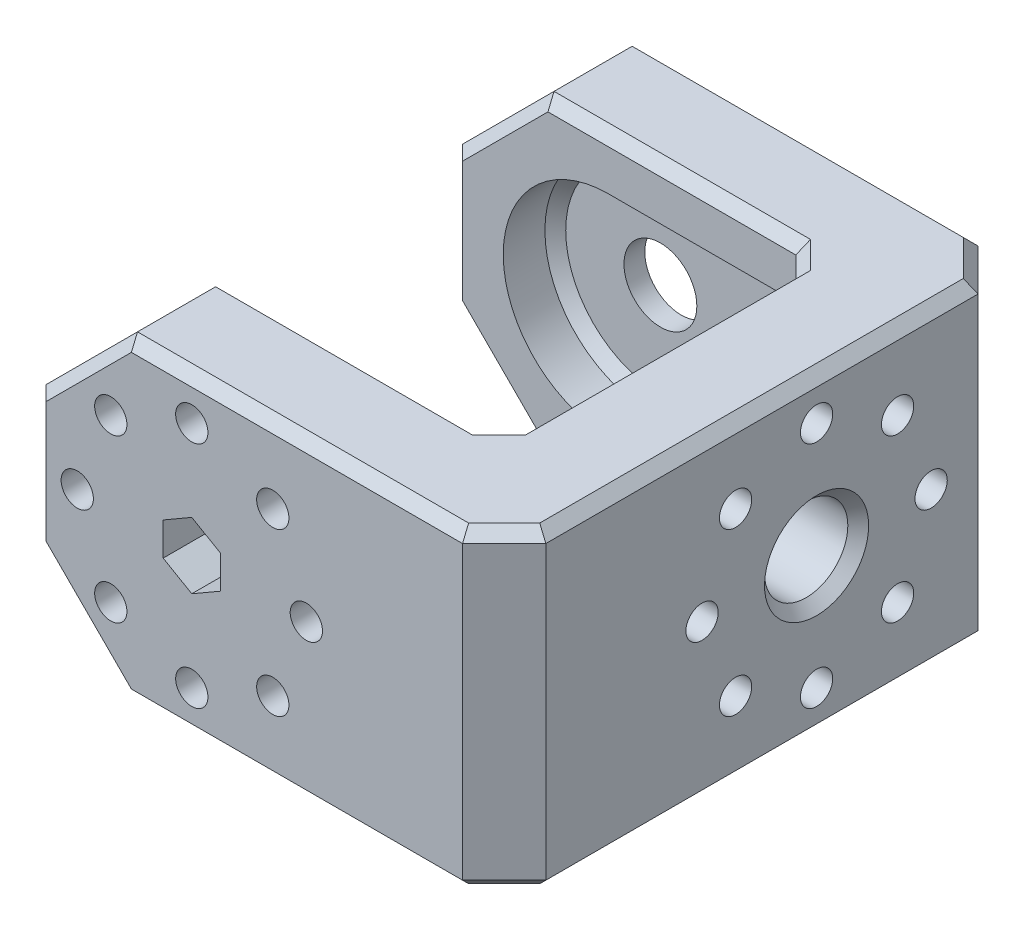
SolidWorks part; units mm, degrees
ref_plane "Alzado" through (0, 0, 0) normal (0, 0, 1) x (1, 0, 0)
ref_plane "Planta" through (0, 0, 0) normal (0, 1, 0) x (1, 0, 0)
ref_plane "Vista lateral" through (0, 0, 0) normal (1, 0, 0) x (0, 0, -1)
sketch "Croquis1" plane through (0, 0, 0) normal (0, 0, 1) x (1, 0, 0)
  line L0 (6.2132, 15) -> (30, 15)
  line L1 (15, -6.2132) -> (15, 6.2132) construction
  line L2 (15, 6.2132) -> (6.2132, 15) construction
  line L3 (6.2132, 15) -> (-6.2132, 15)
  line L4 (-6.2132, 15) -> (-15, 6.2132)
  line L5 (-15, 6.2132) -> (-15, -6.2132)
  line L6 (-15, -6.2132) -> (-6.2132, -15)
  line L7 (-6.2132, -15) -> (6.2132, -15)
  line L8 (6.2132, -15) -> (15, -6.2132) construction
  line L9 (30, 15) -> (30, -15)
  line L10 (30, -15) -> (6.2132, -15)
  circle A0 centre (0, 0) radius 15 construction
  dimension "D1" = 30
  dimension "D2" = 15
extrude "Saliente-Extruir1" add sketch "Croquis1" along normal blind 60
sketch "Croquis2" plane through (0, 15, 0) normal (0, 1, 0) x (1, 0, 0)
  line L0 (-15, -60) -> (-15, 0) construction
  line L1 (-15, -50.5) -> (20, -50.5)
  line L2 (-15, -50.5) -> (-15, -20)
  line L3 (-15, -20) -> (20, -20)
  line L4 (20, -50.5) -> (20, -20)
  line L5 (30, 0) -> (-6.2132, 0) construction
  line L6 (-15, -10.5) -> (20, -10.5)
  line L7 (-15, -10.5) -> (-15, 0)
  line L8 (-15, 0) -> (20, 0)
  line L9 (20, -10.5) -> (20, 0)
  line L10 (30, -60) -> (-6.2132, -60) construction
  line L11 (30, -60) -> (30, 0) construction
  dimension "D1" = 9.5
  dimension "D2" = 30.5
  dimension "D3" = 9.5
  dimension "D4" = 10
extrude "Cortar-Extruir1" cut sketch "Croquis2" against normal through all
sketch "Croquis3" plane through (0, 0, 60) normal (0, 0, 1) x (1, 0, 0)
  circle A0 centre (0, 0) radius 1.5
  dimension "D1" = 3
extrude "Cortar-Extruir2" cut sketch "Croquis3" against normal up to next
sketch "Croquis4" plane through (0, 0, 20) normal (0, 0, 1) x (1, 0, 0)
  line L0 (0, 10.0902) -> (20, 10.0902)
  line L1 (20, -15) -> (20, 15) construction
  line L2 (20, 10.0902) -> (20, -10.0902)
  line L3 (20, -10.0902) -> (0, -10.0902)
  arc A0 (0, 10.0902) -> (0, -10.0902) centre (0, 0) ccw
extrude "Cortar-Extruir3" cut sketch "Croquis4" against normal blind 5
sketch "Croquis5" plane through (30, 0, 0) normal (1, 0, 0) x (0, 0, -1)
  line L0 (-60, 0) -> (49940, 0) construction
  line L1 (-60, -15) -> (-60, 15) construction
  line L2 (-30, 15) -> (-30, -49985) construction
  line L3 (-60, 15) -> (0, 15) construction
  circle A0 centre (-30, 0) radius 4
  circle A1 centre (-30, 0) radius 11 construction
  circle A2 centre (-30, 11) radius 1.55
  circle A3 centre (-22.2218, 7.7782) radius 1.55
  circle A4 centre (-19, 0) radius 1.55
  circle A5 centre (-22.2218, -7.7782) radius 1.55
  circle A6 centre (-30, -11) radius 1.55
  circle A7 centre (-37.7782, -7.7782) radius 1.55
  circle A8 centre (-41, 0) radius 1.55
  circle A9 centre (-37.7782, 7.7782) radius 1.55
  point P4 (-60, 0)
  point P9 (-30, 15)
  point P32 (-30, 0)
  dimension "D1" = 8
  dimension "D2" = 22
  dimension "D3" = 3.1
  dimension "D4" = 8
extrude "Cortar-Extruir4" cut sketch "Croquis5" against normal blind 10
sketch "Croquis6" plane through (20, 0, 0) normal (-1, 0, 0) x (0, 0, 1)
  line L0 (40.0235, 5.5328) -> (40.8454, 8.6)
  line L1 (33.1754, 11) -> (31.5877, 13.75)
  line L2 (31.5877, 13.75) -> (28.4123, 13.75)
  line L3 (28.4123, 13.75) -> (26.8246, 11)
  line L4 (26.8246, 11) -> (28.4123, 8.25)
  line L5 (28.4123, 8.25) -> (31.5877, 8.25)
  line L6 (31.5877, 8.25) -> (33.1754, 11)
  line L7 (40.8454, 8.6) -> (38.6, 10.8454)
  line L8 (38.6, 10.8454) -> (35.5328, 10.0235)
  line L9 (35.5328, 10.0235) -> (34.7109, 6.9563)
  line L10 (34.7109, 6.9563) -> (36.9563, 4.7109)
  line L11 (36.9563, 4.7109) -> (40.0235, 5.5328)
  line L12 (41, -3.1754) -> (43.75, -1.5877)
  line L13 (43.75, -1.5877) -> (43.75, 1.5877)
  line L14 (43.75, 1.5877) -> (41, 3.1754)
  line L15 (41, 3.1754) -> (38.25, 1.5877)
  line L16 (38.25, 1.5877) -> (38.25, -1.5877)
  line L17 (38.25, -1.5877) -> (41, -3.1754)
  line L18 (35.5328, -10.0235) -> (38.6, -10.8454)
  line L19 (38.6, -10.8454) -> (40.8454, -8.6)
  line L20 (40.8454, -8.6) -> (40.0235, -5.5328)
  line L21 (40.0235, -5.5328) -> (36.9563, -4.7109)
  line L22 (36.9563, -4.7109) -> (34.7109, -6.9563)
  line L23 (34.7109, -6.9563) -> (35.5328, -10.0235)
  line L24 (26.8246, -11) -> (28.4123, -13.75)
  line L25 (28.4123, -13.75) -> (31.5877, -13.75)
  line L26 (31.5877, -13.75) -> (33.1754, -11)
  line L27 (33.1754, -11) -> (31.5877, -8.25)
  line L28 (31.5877, -8.25) -> (28.4123, -8.25)
  line L29 (28.4123, -8.25) -> (26.8246, -11)
  line L30 (19.9765, -5.5328) -> (19.1546, -8.6)
  line L31 (19.1546, -8.6) -> (21.4, -10.8454)
  line L32 (21.4, -10.8454) -> (24.4672, -10.0235)
  line L33 (24.4672, -10.0235) -> (25.2891, -6.9563)
  line L34 (25.2891, -6.9563) -> (23.0437, -4.7109)
  line L35 (23.0437, -4.7109) -> (19.9765, -5.5328)
  line L36 (19, 3.1754) -> (16.25, 1.5877)
  line L37 (16.25, 1.5877) -> (16.25, -1.5877)
  line L38 (16.25, -1.5877) -> (19, -3.1754)
  line L39 (19, -3.1754) -> (21.75, -1.5877)
  line L40 (21.75, -1.5877) -> (21.75, 1.5877)
  line L41 (21.75, 1.5877) -> (19, 3.1754)
  line L42 (24.4672, 10.0235) -> (21.4, 10.8454)
  line L43 (21.4, 10.8454) -> (19.1546, 8.6)
  line L44 (19.1546, 8.6) -> (19.9765, 5.5328)
  line L45 (19.9765, 5.5328) -> (23.0437, 4.7109)
  line L46 (23.0437, 4.7109) -> (25.2891, 6.9563)
  line L47 (25.2891, 6.9563) -> (24.4672, 10.0235)
  circle A0 centre (30, 11) radius 2.75 construction
  circle A1 centre (37.7782, 7.7782) radius 2.75 construction
  circle A2 centre (41, 0) radius 2.75 construction
  circle A3 centre (37.7782, -7.7782) radius 2.75 construction
  circle A4 centre (30, -11) radius 2.75 construction
  circle A5 centre (22.2218, -7.7782) radius 2.75 construction
  circle A6 centre (19, 0) radius 2.75 construction
  circle A7 centre (22.2218, 7.7782) radius 2.75 construction
  point P68 (30, 0)
  dimension "D1" = 5.5
  dimension "D2" = 8
extrude "Cortar-Extruir5" cut sketch "Croquis6" against normal blind 5
sketch "Croquis7" plane through (0, 0, 60) normal (0, 0, 1) x (1, 0, 0)
  circle A0 centre (0, 11) radius 1.55
  circle A1 centre (0, 0) radius 1.5 construction
  circle A2 centre (7.7782, 7.7782) radius 1.55
  circle A3 centre (11, 0) radius 1.55
  circle A4 centre (7.7782, -7.7782) radius 1.55
  circle A5 centre (0, -11) radius 1.55
  circle A6 centre (-7.7782, -7.7782) radius 1.55
  circle A7 centre (-11, 0) radius 1.55
  circle A8 centre (-7.7782, 7.7782) radius 1.55
  point P21 (0, 0)
  dimension "D1" = 11
  dimension "D3" = 3.1
  dimension "D2" = 8
extrude "Cortar-Extruir6" cut sketch "Croquis7" against normal up to next
sketch "Croquis8" plane through (0, 0, 50.5) normal (0, 0, -1) x (-1, 0, 0)
  line L0 (6.9563, 4.7109) -> (10.0235, 5.5328)
  line L1 (3.1754, 11) -> (1.5877, 13.75)
  line L2 (1.5877, 13.75) -> (-1.5877, 13.75)
  line L3 (-1.5877, 13.75) -> (-3.1754, 11)
  line L4 (-3.1754, 11) -> (-1.5877, 8.25)
  line L5 (-1.5877, 8.25) -> (1.5877, 8.25)
  line L6 (1.5877, 8.25) -> (3.1754, 11)
  line L7 (10.0235, 5.5328) -> (10.8454, 8.6)
  line L8 (10.8454, 8.6) -> (8.6, 10.8454)
  line L9 (8.6, 10.8454) -> (5.5328, 10.0235)
  line L10 (5.5328, 10.0235) -> (4.7109, 6.9563)
  line L11 (4.7109, 6.9563) -> (6.9563, 4.7109)
  line L12 (8.25, -1.5877) -> (11, -3.1754)
  line L13 (11, -3.1754) -> (13.75, -1.5877)
  line L14 (13.75, -1.5877) -> (13.75, 1.5877)
  line L15 (13.75, 1.5877) -> (11, 3.1754)
  line L16 (11, 3.1754) -> (8.25, 1.5877)
  line L17 (8.25, 1.5877) -> (8.25, -1.5877)
  line L18 (4.7109, -6.9563) -> (5.5328, -10.0235)
  line L19 (5.5328, -10.0235) -> (8.6, -10.8454)
  line L20 (8.6, -10.8454) -> (10.8454, -8.6)
  line L21 (10.8454, -8.6) -> (10.0235, -5.5328)
  line L22 (10.0235, -5.5328) -> (6.9563, -4.7109)
  line L23 (6.9563, -4.7109) -> (4.7109, -6.9563)
  line L24 (-1.5877, -8.25) -> (-3.1754, -11)
  line L25 (-3.1754, -11) -> (-1.5877, -13.75)
  line L26 (-1.5877, -13.75) -> (1.5877, -13.75)
  line L27 (1.5877, -13.75) -> (3.1754, -11)
  line L28 (3.1754, -11) -> (1.5877, -8.25)
  line L29 (1.5877, -8.25) -> (-1.5877, -8.25)
  line L30 (-6.9563, -4.7109) -> (-10.0235, -5.5328)
  line L31 (-10.0235, -5.5328) -> (-10.8454, -8.6)
  line L32 (-10.8454, -8.6) -> (-8.6, -10.8454)
  line L33 (-8.6, -10.8454) -> (-5.5328, -10.0235)
  line L34 (-5.5328, -10.0235) -> (-4.7109, -6.9563)
  line L35 (-4.7109, -6.9563) -> (-6.9563, -4.7109)
  line L36 (-8.25, 1.5877) -> (-11, 3.1754)
  line L37 (-11, 3.1754) -> (-13.75, 1.5877)
  line L38 (-13.75, 1.5877) -> (-13.75, -1.5877)
  line L39 (-13.75, -1.5877) -> (-11, -3.1754)
  line L40 (-11, -3.1754) -> (-8.25, -1.5877)
  line L41 (-8.25, -1.5877) -> (-8.25, 1.5877)
  line L42 (-4.7109, 6.9563) -> (-5.5328, 10.0235)
  line L43 (-5.5328, 10.0235) -> (-8.6, 10.8454)
  line L44 (-8.6, 10.8454) -> (-10.8454, 8.6)
  line L45 (-10.8454, 8.6) -> (-10.0235, 5.5328)
  line L46 (-10.0235, 5.5328) -> (-6.9563, 4.7109)
  line L47 (-6.9563, 4.7109) -> (-4.7109, 6.9563)
  circle A0 centre (0, 11) radius 2.75 construction
  circle A1 centre (7.7782, 7.7782) radius 2.75 construction
  circle A2 centre (11, 0) radius 2.75 construction
  circle A3 centre (7.7782, -7.7782) radius 2.75 construction
  circle A4 centre (0, -11) radius 2.75 construction
  circle A5 centre (-7.7782, -7.7782) radius 2.75 construction
  circle A6 centre (-11, 0) radius 2.75 construction
  circle A7 centre (-7.7782, 7.7782) radius 2.75 construction
  point P67 (0, 0)
  dimension "D1" = 5.5
  dimension "D2" = 8
extrude "Cortar-Extruir7" cut sketch "Croquis8" against normal blind 5
sketch "Croquis9" plane through (0, 0, 60) normal (0, 0, 1) x (1, 0, 0)
  line L1 (0, 3.1754) -> (-2.75, 1.5877)
  line L2 (-2.75, 1.5877) -> (-2.75, -1.5877)
  line L3 (-2.75, -1.5877) -> (0, -3.1754)
  line L4 (0, -3.1754) -> (2.75, -1.5877)
  line L5 (2.75, -1.5877) -> (2.75, 1.5877)
  line L6 (2.75, 1.5877) -> (0, 3.1754)
  circle A0 centre (0, 0) radius 2.75 construction
  dimension "D1" = 5.5
extrude "Cortar-Extruir8" cut sketch "Croquis9" against normal blind 5
sketch "Croquis10" plane through (0, 0, 10.5) normal (0, 0, -1) x (-1, 0, 0)
  circle A0 centre (0, 0) radius 3.5
  dimension "D1" = 7
extrude "Cortar-Extruir9" cut sketch "Croquis10" against normal up to next
sketch "Croquis11" plane through (0, 0, 10.5) normal (0, 0, -1) x (-1, 0, 0)
  circle A0 centre (0, 0) radius 8.2213
extrude "Cortar-Extruir10" cut sketch "Croquis11" against normal offset from surface (2.5 mm away) 2 up to face at (3.5, 0, 15)
sketch "Croquis12" plane through (0, 0, 15) normal (0, 0, 1) x (1, 0, 0)
  line L1 (-1.2, 8.6) -> (1.2, 8.6)
  line L2 (-1.2, 8.6) -> (-1.2, 7.4)
  line L3 (-1.2, 7.4) -> (1.2, 7.4)
  line L4 (1.2, 8.6) -> (1.2, 7.4)
  line L5 (-1.2, 8.6) -> (1.2, 7.4) construction
  line L6 (-1.2, 7.4) -> (1.2, 8.6) construction
  point P0 (0, 8)
  dimension "D1" = 1.2
  dimension "D2" = 2.4
  dimension "D3" = 8
extrude "Cortar-Extruir11" cut sketch "Croquis12" against normal blind 3
sketch "Croquis13" plane through (0, -15, 0) normal (0, -1, 0) x (1, 0, 0)
  line L1 (20, 10.5) -> (30, 10.5)
  line L2 (20, 10.5) -> (20, 0)
  line L3 (20, 0) -> (30, 0)
  line L4 (30, 10.5) -> (30, 0)
extrude "Cortar-Extruir12" cut sketch "Croquis13" against normal through all
chamfer "Chaflán5" distance 1 angle 45 2 edges at (20, 4, 30) (30, 4, 30)
chamfer "Chaflán4" distance 0.25 angle 45 4 edges at (1.2, 8, 15) (0, 8.6, 15) (-1.2, 8, 15) (0, 7.4, 15)
chamfer "Chaflán1" distance 2 angle 45 3 edges at (20, 0, 50.5) (20, -12.5451, 20) (20, 12.5451, 20)
chamfer "Chaflán2" distance 2 angle 45 1 edges at (20, 0, 15)
chamfer "Chaflán6" distance 4 angle 45 2 edges at (30, 0, 10.5) (30, 0, 60)
chamfer "Chaflán7" distance 1 angle 45 3 edges at (9, 10.0902, 15) (-10.0902, 0, 15) (9, -10.0902, 15)
chamfer "Chaflán3" distance 1 angle 45 32 edges at (30, 15, 35.25) (30, -15, 35.25) (19, -15, 49.5) (20, -15, 35.25) (5.8934, -15, 20) (-10.6066, -10.6066, 20) (-15, 0, 20) (-10.6066, 10.6066, 20) (5.8934, 15, 20) (5.8934, -15, 50.5) (-10.6066, -10.6066, 50.5) (-15, 0, 50.5) (-10.6066, 10.6066, 50.5) (5.8934, 15, 50.5) (19, 15, 49.5) (20, 15, 35.25) (9.8934, -15, 60) (-10.6066, -10.6066, 60) (-15, 0, 60) (-10.6066, 10.6066, 60) (9.8934, 15, 60) (9.8934, -15, 10.5) (-10.6066, -10.6066, 10.5) (-15, 0, 10.5) (-10.6066, 10.6066, 10.5) (9.8934, 15, 10.5) (19, -15, 21) (19, 15, 21) (28, -15, 12.5) (28, -15, 58) (28, 15, 58) (28, 15, 12.5)
